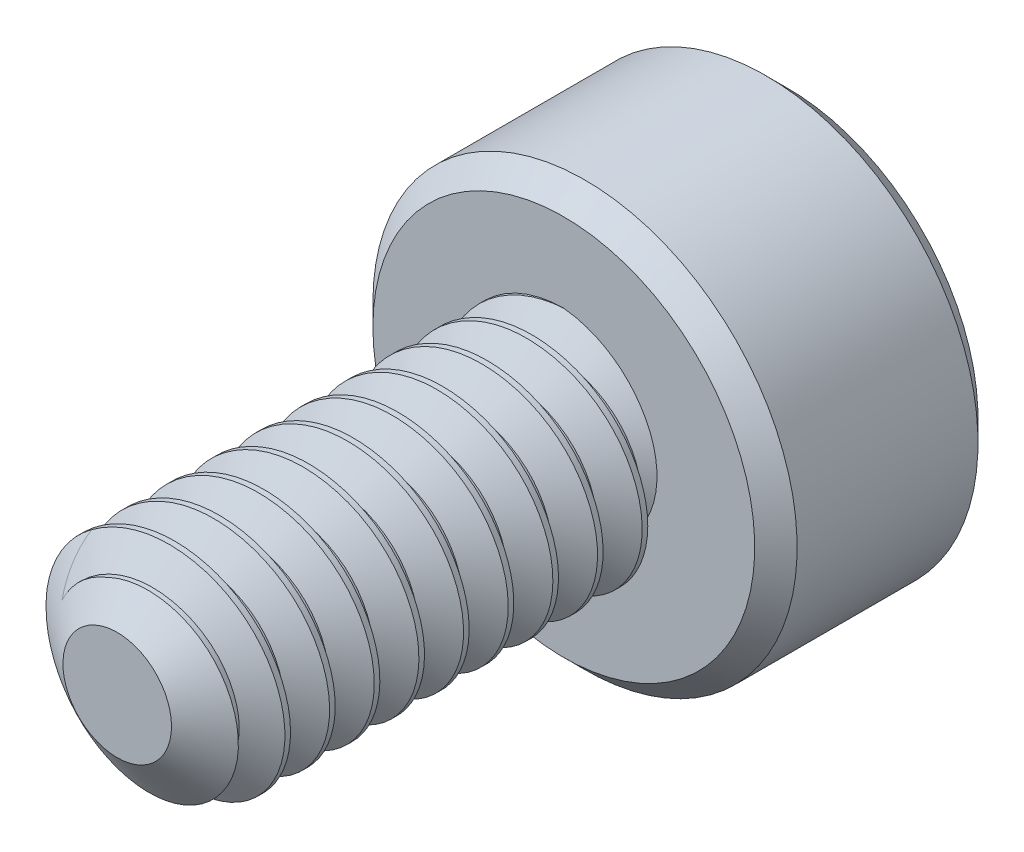
SolidWorks part; units mm, degrees
other "DetailItem1"
ref_plane "Front Plane" through (0, 0, 0) normal (0, 0, 1) x (1, 0, 0)
ref_plane "Top Plane" through (0, 0, 0) normal (0, 1, 0) x (1, 0, 0)
ref_plane "Right Plane" through (0, 0, 0) normal (1, 0, 0) x (0, 0, -1)
sketch "Sketch1" plane through (0, 0, 0) normal (0, 0, 1) x (1, 0, 0)
  circle A0 centre (0, 0) radius 1
  dimension "OD" = 2
extrude "Extrude1" add sketch "Sketch1" against normal blind 4
sketch "Sketch2" plane through (0, 0, 0) normal (0, 0, 1) x (1, 0, 0)
  circle A0 centre (0, 0) radius 1 construction
  circle A1 centre (0, 0) radius 1
curve "Helix/Spiral1" pitch 0.4 height 4.4 radius 1 centre (0, 0, 0) axis (0, 0, -1) start towards (0, 1, 0) parameters "pitch"=0.4
sketch "Sketch3" plane through (0, 0, 0) normal (1, 0, 0) x (0, 0, -1)
  line L0 (-0.35, 1) -> (-0.2, 0.7402)
  line L1 (-0.2, 0.7402) -> (-0.15, 0.7402)
  line L2 (-0.15, 0.7402) -> (0, 1)
  line L3 (-0.35, 1) -> (0, 1)
  line L4 (-0.175, 1) -> (-0.175, 0.7402) construction
  line L5 (-0.275, 0.8701) -> (-0.075, 0.8701) construction
  line L6 (0, 1) -> (0, -1) construction
  dimension "D1" = 0.05
  dimension "D2" = 0.2
  dimension "D3" = 60
sweep "Cut-Sweep1" cut profiles "Sketch3" path "Helix/Spiral1"
sketch "Sketch4" plane through (0, 0, 0) normal (1, 0, 0) x (0, 0, -1)
  line L0 (0.3598, 1) -> (0, 0.4862)
  line L1 (0, 0.4862) -> (0, 1)
  line L2 (0.3598, 1) -> (0, 1)
  line L3 (-0.35, 1) -> (0, 1) construction
  line L4 (0, 0) -> (7.0209, 0) construction
  dimension "D1" = 55
  dimension "D2" = 0.254
revolve "Cut-Revolve1" cut sketch "Sketch4" angle 360 about L4
sketch "Sketch6" plane through (0, 0, -4) normal (0, 0, -1) x (-1, 0, 0)
  circle A0 centre (0, 0) radius 1.9
  dimension "head dia" = 3.8
extrude "Extrude2" add sketch "Sketch6" along normal blind 2
sketch "Sketch7" plane through (0, 0, -6) normal (0, 0, -1) x (-1, 0, 0)
  line L1 (0, 0.866) -> (-0.75, 0.433)
  line L2 (-0.75, 0.433) -> (-0.75, -0.433)
  line L3 (-0.75, -0.433) -> (0, -0.866)
  line L4 (0, -0.866) -> (0.75, -0.433)
  line L5 (0.75, -0.433) -> (0.75, 0.433)
  line L6 (0.75, 0.433) -> (0, 0.866)
  circle A0 centre (0, 0) radius 0.75 construction
  dimension "hex dia" = 1.5
extrude "Cut-Extrude1" cut sketch "Sketch7" against normal blind 1.125
sketch "Sketch8" plane through (0, 0, -6) normal (0, 0, -1) x (-1, 0, 0)
  circle A0 centre (0, 0) radius 0.866
extrude "Cut-Extrude2" cut sketch "Sketch8" against normal through all draft 45
chamfer "Chamfer1" distance 0.19 angle 45 2 edges at (-1.9, 0, -6) (-1.9, 0, -4)
sketch "Sketch10" plane through (0, 0, -4) normal (0, 0, 1) x (1, 0, 0)
  circle A1 centre (0, 0) radius 1
  circle A2 centre (0, 0) radius 1
  dimension "D1" = 0
ref_plane "Plane1" through (0, 0, 0) normal (0, 0, 1) x (1, 0, 0)
extrude "partial thread" [suppressed] add sketch "Sketch10" along normal up to surface (2 mm away) separate body up to plane "Plane1"
chamfer "Chamfer2" [suppressed] distance 0.04 angle 45
combine bodies "Combine1" [suppressed] operation type add bodies to combine 107 108
sketch "Sketch9" plane through (0, 0, 0) normal (1, 0, 0) x (0, 0, -1)
  line L0 (0, 1) -> (0, -1) construction
  line L1 (1, 1) -> (1, -1) construction
  dimension "D1" = 1
equation "\"D3@Helix/Spiral1\" = \"screw length@Extrude1\"+\"pitch@Helix/Spiral1\""
equation "\"D1@Sketch3\" = \"pitch@Helix/Spiral1\"*.125"
equation "\"D2@Sketch3\" = \"pitch@Helix/Spiral1\"*.5"
equation "\"D1@Cut-Extrude1\" = \"hex dia@Sketch7\"*.75"
equation "\"D1@Chamfer1\" = \"head dia@Sketch6\"*.05"
equation "\"D1@Sketch9\" = \"pitch@Helix/Spiral1\"*2.5"
equation "\"D1@Chamfer2\"=\"OD@Sketch1\"*.02"
